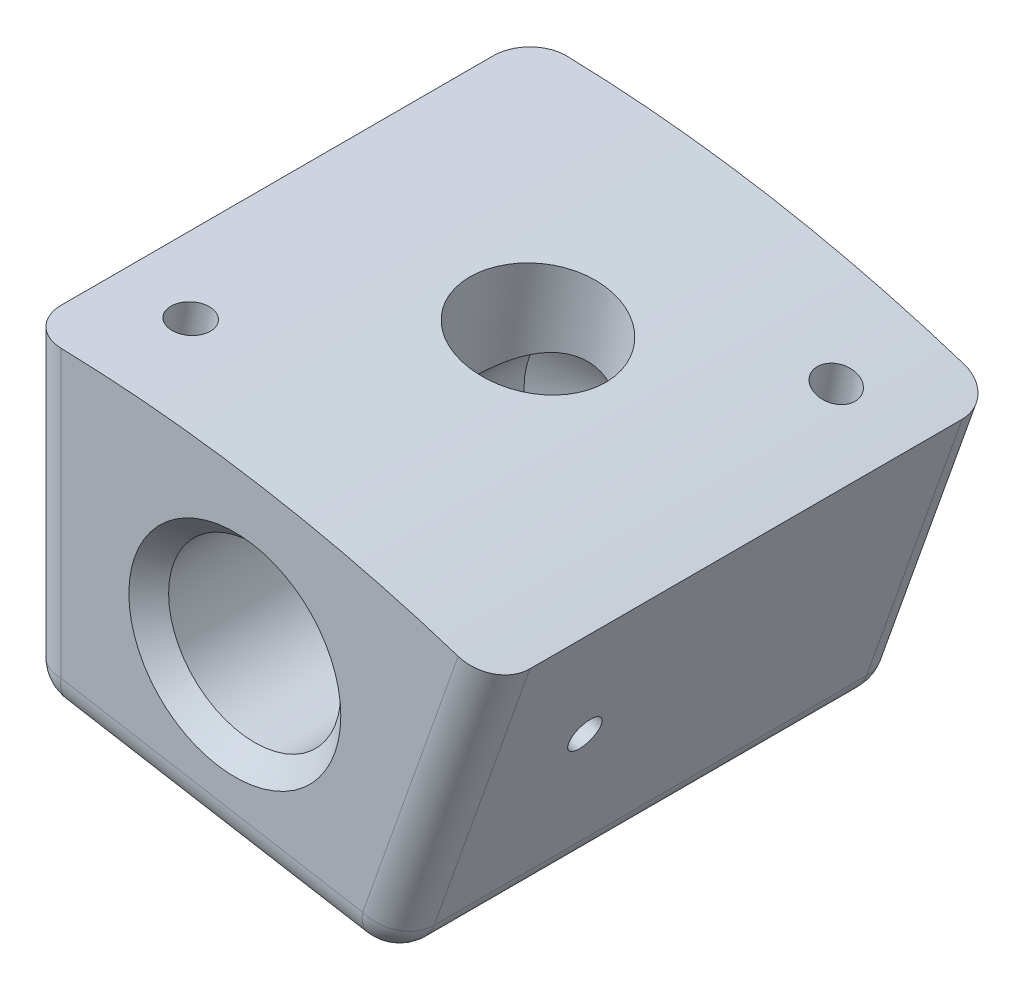
SolidWorks part; units mm, degrees
material "6061-T6 (SS)"
ref_plane "Front Plane" through (0, 0, 0) normal (0, 0, 1) x (1, 0, 0)
ref_plane "Top Plane" through (0, 0, 0) normal (0, 1, 0) x (1, 0, 0)
ref_plane "Right Plane" through (0, 0, 0) normal (1, 0, 0) x (0, 0, -1)
sketch "Sketch1" plane through (0, 0, 0) normal (0, 0, 1) x (1, 0, 0)
  line L0 (0, 96.8375) -> (0, 74.9305)
  line L1 (32.3511, 91.2738) -> (25.0325, 70.6255)
  line L2 (0, 74.9305) -> (0, 85.884)
  line L3 (0, 74.9305) -> (25.0325, 70.6255)
  circle A0 centre (0, 0) radius 96.8375
  dimension "D1" = 25.4
  dimension "D4" = 193.675
  dimension "D2" = 21.59
extrude "Boss-Extrude2" add sketch "Sketch1" along normal blind 34.925 contours L1 A0 L0 L3 region at (14.5097, 84.3693, 0)
sketch "Sketch5" plane through (0, 0, 34.925) normal (0, 0, 1) x (1, 0, 0)
  line L1 (12.5163, 72.778) -> (16.413, 95.4364) construction
  line L2 (0, 74.9305) -> (25.0325, 70.6255) construction
  arc A2 (0, 96.8375) -> (32.3511, 91.2738) centre (0, 0) cw
  arc A3 (32.3511, 91.2738) -> (0, 96.8375) centre (0, 0) ccw construction
  point P3 (14.5296, 84.4847)
  dimension "D1" = 85.725
hole_wizard "1/4-18 NPSM Tapped Hole1" positions "3DSketch3" profile "Sketch7" tap size "1/4-18 NPSM" standard "ANSI Inch"
sketch3d "3DSketch3"
  point P0 (14.5296, 84.4847, 34.925)
cosmetic thread "Hole Thread2" parameters "D1"=24.13, "D2"=13.3604
sketch "Sketch7" plane through (14.5296, 84.4847, 34.925) normal (1, 0, 0) x (0, -1, 0)
  line L0 (0, 0) -> (0, 29.4793)
  line L1 (0, 29.4793) -> (5.9436, 25.908)
  line L2 (5.9436, 25.908) -> (5.9436, 1.3716)
  line L3 (5.9436, 1.3716) -> (7.3152, 0)
  line L5 (7.3152, 0) -> (0, 0)
  line L6 (-5.9436, 1.3716) -> (-7.3152, 0) construction
  line L10 (0, 29.4793) -> (-5.9436, 25.908) construction
  line L11 (0, -6.35) -> (0, 107.95) construction
  dimension "Tap Drill Dia." = 11.8872
  dimension "Tap Drill Depth" = 25.908
  dimension "Near C'Sink Dia." = 14.6304
  dimension "Near C'Sink Angle" = 90
  dimension "Drill Angle" = 118
sketch "Sketch8" plane through (12.5163, 72.778, 0) normal (-0.1695, -0.9855, 0) x (-0.9855, 0.1695, 0)
  circle A0 centre (0, -12.7) radius 4.7625
extrude "Cut-Extrude1" [suppressed] cut sketch "Sketch8" against normal blind 25.4 contours A0
sketch "Sketch11" [suppressed] plane through (12.6328, 128.2508, 0) normal (-0.098, -0.9952, 0) x (-0.9952, 0.098, 0)
  circle A0 centre (0, -12.7) radius 4.7625
extrude "Boss-Extrude5" [suppressed] add sketch "Sketch11" against normal blind 5.08
ref_plane "Plane1" through (16.413, 95.4364, 0) normal (0.1695, 0.9855, 0) x (0.9855, -0.1695, 0)
sketch "Sketch12" plane through (16.413, 95.4364, 0) normal (0.1695, 0.9855, 0) x (0.9855, -0.1695, 0)
  line L0 (16.413, 0) -> (-16.413, 0) construction
  line L1 (16.413, -34.925) -> (16.413, 0) construction
  circle A0 centre (0, -15.875) radius 4.7625
  dimension "D1" = 9.525
  dimension "D2" = 15.875
  dimension "D3" = 16.413
extrude "Cut-Extrude2" cut sketch "Sketch12" against normal up to next contours A0
fillet "Fillet1" radius 2.54 1 edges at (0, 85.884, 34.925)
fillet "Fillet2" radius 2.54 3 edges at (0, 74.9305, 16.1925) (0.7439, 74.8026, 34.1811) (13.7863, 72.5596, 34.925)
fillet "Fillet3" radius 2.54 3 edges at (25.0325, 70.6255, 16.1925) (25.2847, 71.337, 34.1811) (29.1223, 82.1643, 34.925)
fillet "Fillet4" radius 2.54 5 edges at (0, 86.9543, 0) (0.5977, 75.4342, 0) (12.5163, 72.778, 0) (24.6374, 71.2999, 0) (29.0493, 81.9584, 0)
hole_wizard "Tap Drill for #6-32 Tap1" positions "Sketch14" profile "Sketch13" hole size "#6-32" standard "ANSI Inch"
sketch "Sketch14" plane through (16.413, 95.4364, 0) normal (0.1695, 0.9855, 0) x (0.9855, -0.1695, 0)
  line L0 (0, 0) -> (0, -35.0993) construction
  line L2 (0, -15.875) -> (-16.413, -15.875) construction
  line L3 (-16.413, -32.385) -> (-16.413, -2.54) construction
  line L4 (16.413, -32.385) -> (16.413, -2.54) construction
  point P15 (-11.333, -28.575)
  point P17 (11.333, -6.35)
  dimension "D1" = 12.7
  dimension "D2" = 5.08
  dimension "D3" = 5.08
  dimension "D4" = 9.525
sketch "Sketch13" plane through (27.5821, 93.5156, 6.35) normal (0, 0, 1) x (-0.9855, 0.1695, 0)
  line L0 (0, 0) -> (0, 10.4647)
  line L1 (0, 10.4647) -> (1.3525, 9.652)
  line L2 (1.3525, 9.652) -> (1.3525, 0)
  line L5 (1.3525, 0) -> (0, 0)
  line L10 (0, 10.4647) -> (-1.3526, 9.652) construction
  line L11 (0, -6.35) -> (0, 107.95) construction
  dimension "Hole Dia." = 2.7051
  dimension "Hole Depth" = 9.652
  dimension "Drill Angle" = 118
hole_wizard "Tap Drill for #4-40 Tap1" positions "Sketch15" profile "Sketch17" hole size "#4-40" standard "ANSI Inch"
sketch "Sketch15" plane through (0, 0, 0) normal (0.9425, -0.3341, 0) x (0, 0, -1)
  line L0 (0, 96.8042) -> (0, 77.071) construction
  line L1 (-32.385, 96.8375) -> (-2.54, 96.8375) construction
  point P0 (-25.4, 87.3125)
  dimension "D1" = 25.4
  dimension "D2" = 9.525
sketch "Sketch17" plane through (29.169, 82.2961, 25.4) normal (0, 0, 1) x (0.3341, 0.9425, 0)
  line L0 (0, 0) -> (0, 26.0792)
  line L1 (0, 26.0792) -> (1.1303, 25.4)
  line L2 (1.1303, 25.4) -> (1.1303, 0)
  line L5 (1.1303, 0) -> (0, 0)
  line L10 (0, 26.0792) -> (-1.1303, 25.4) construction
  line L11 (0, -6.35) -> (0, 107.95) construction
  dimension "Hole Dia." = 2.2606
  dimension "Hole Depth" = 25.4
  dimension "Drill Angle" = 118
